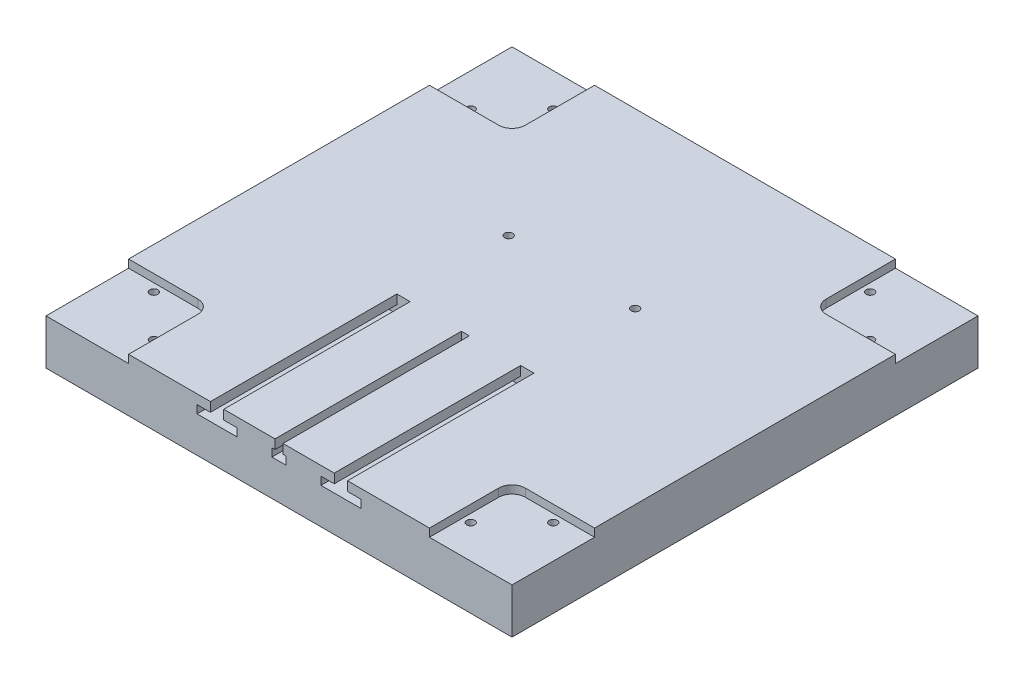
SolidWorks part; units mm, degrees
ref_plane "Front Plane" through (0, 0, 0) normal (0, 0, 1) x (1, 0, 0)
ref_plane "Top Plane" through (0, 0, 0) normal (0, 1, 0) x (1, 0, 0)
ref_plane "Right Plane" through (0, 0, 0) normal (1, 0, 0) x (0, 0, -1)
sketch "Sketch1" plane through (0, 0, 0) normal (0, 1, 0) x (1, 0, 0)
  line L0 (0, 87.5) -> (0, -87.5) construction
  line L1 (-87.5, 87.5) -> (87.5, 87.5)
  line L2 (-87.5, 87.5) -> (-87.5, -87.5)
  line L3 (-87.5, -87.5) -> (87.5, -87.5)
  line L4 (87.5, 87.5) -> (87.5, -87.5)
  line L5 (-87.5, 87.5) -> (87.5, -87.5) construction
  line L6 (-87.5, -87.5) -> (87.5, 87.5) construction
  line L15 (-87.5, 0) -> (87.5, 0) construction
  point P0 (0, 0)
  dimension "D1" = 175
  dimension "D2" = 175
extrude "Boss-Extrude2" add sketch "Sketch1" along normal blind 20
sketch "Sketch7" plane through (0, 20, 0) normal (0, 1, 0) x (1, 0, 0)
  line L0 (0, 87.5) -> (0, -87.5) construction
  line L1 (-87.5, 87.5) -> (-56.5, 87.5)
  line L2 (-87.5, 87.5) -> (-87.5, 56.5)
  line L3 (-87.5, 56.5) -> (-61.5, 56.5)
  line L4 (-56.5, 87.5) -> (-56.5, 61.5)
  line L5 (87.5, 87.5) -> (-87.5, 87.5) construction
  line L6 (-87.5, -87.5) -> (87.5, -87.5) construction
  line L7 (-87.5, 0) -> (87.5, 0) construction
  line L8 (-87.5, 87.5) -> (-87.5, -87.5) construction
  line L9 (87.5, -87.5) -> (87.5, 87.5) construction
  line L10 (87.5, 56.5) -> (61.5, 56.5)
  line L11 (56.5, 87.5) -> (56.5, 61.5)
  line L12 (87.5, 87.5) -> (56.5, 87.5)
  line L13 (87.5, 87.5) -> (87.5, 56.5)
  line L14 (87.5, -87.5) -> (87.5, -56.5)
  line L15 (87.5, -87.5) -> (56.5, -87.5)
  line L16 (56.5, -87.5) -> (56.5, -61.5)
  line L17 (87.5, -56.5) -> (61.5, -56.5)
  line L18 (-56.5, -87.5) -> (-56.5, -61.5)
  line L19 (-87.5, -56.5) -> (-61.5, -56.5)
  line L20 (-87.5, -87.5) -> (-87.5, -56.5)
  line L21 (-87.5, -87.5) -> (-56.5, -87.5)
  arc A0 (-61.5, 56.5) -> (-56.5, 61.5) centre (-61.5, 61.5) ccw
  arc A1 (61.5, 56.5) -> (56.5, 61.5) centre (61.5, 61.5) cw
  arc A2 (61.5, -56.5) -> (56.5, -61.5) centre (61.5, -61.5) ccw
  arc A3 (-61.5, -56.5) -> (-56.5, -61.5) centre (-61.5, -61.5) cw
  point P7 (-56.5, 56.5)
  point P38 (-56.5, -56.5)
  dimension "D3" = 5
  dimension "D1" = 31
  dimension "D2" = 31
extrude "Cut-Extrude6" cut sketch "Sketch7" against normal blind 3
sketch "Sketch8" plane through (0, 17, 0) normal (0, 1, 0) x (1, 0, 0)
  line L0 (-75, -62.5) -> (-75, -56.5) construction
  line L5 (-61.5, -56.5) -> (-87.5, -56.5) construction
  line L6 (-62.5, -75) -> (-56.5, -75) construction
  line L7 (-56.5, -87.5) -> (-56.5, -61.5) construction
  line L8 (-87.5, -87.5) -> (-56.5, -87.5) construction
  line L9 (-87.5, -56.5) -> (-87.5, -87.5) construction
  line L10 (0, 87.5) -> (0, -87.5) construction
  line L11 (56.5, 87.5) -> (-56.5, 87.5) construction
  line L12 (-56.5, -87.5) -> (56.5, -87.5) construction
  line L13 (62.5, -75) -> (56.5, -75) construction
  line L14 (75, -62.5) -> (75, -56.5) construction
  line L15 (-87.5, 0) -> (87.5, 0) construction
  line L16 (-87.5, 56.5) -> (-87.5, -56.5) construction
  line L17 (87.5, -56.5) -> (87.5, 56.5) construction
  circle A0 centre (-75, -59.5) radius 1.5
  circle A1 centre (-59.5, -75) radius 1.5
  circle A2 centre (59.5, -75) radius 1.5
  circle A3 centre (75, -59.5) radius 1.5
  circle A4 centre (59.5, 75) radius 1.5
  circle A5 centre (75, 59.5) radius 1.5
  circle A6 centre (-59.5, 75) radius 1.5
  circle A7 centre (-75, 59.5) radius 1.5
  dimension "D3" = 3
  dimension "D4" = 3
  dimension "D1" = 28
  dimension "D2" = 28
  dimension "D5" = 12.5
  dimension "D6" = 12.5
extrude "Cut-Extrude7" cut sketch "Sketch8" against normal up to next
sketch "Sketch9" plane through (0, 0, 87.5) normal (0, 0, 1) x (1, 0, 0)
  line L0 (0, 20) -> (0, 0) construction
  line L1 (-56.5, 20) -> (56.5, 20) construction
  line L2 (0, 10) -> (-46.5, 10) construction
  line L3 (-46.5, 20) -> (46.5, 20)
  line L4 (-46.5, 20) -> (-46.5, 0)
  line L5 (-46.5, 0) -> (46.5, 0)
  line L6 (46.5, 20) -> (46.5, 0)
  line L7 (-46.5, 20) -> (46.5, 0) construction
  line L8 (-46.5, 0) -> (46.5, 20) construction
  line L9 (-46.5, 10) -> (0, 10) construction
  line L10 (-20.75, 16.5) -> (-15.75, 16.5)
  line L11 (-23.25, 10) -> (-23.25, 20) construction
  line L12 (-30.75, 16.5) -> (-25.75, 16.5)
  line L13 (-30.75, 16.5) -> (-30.75, 13.5)
  line L14 (-30.75, 13.5) -> (-15.75, 13.5)
  line L15 (-15.75, 16.5) -> (-15.75, 13.5)
  line L16 (-30.75, 16.5) -> (-15.75, 13.5) construction
  line L17 (-30.75, 13.5) -> (-15.75, 16.5) construction
  line L18 (-25.75, 20) -> (-20.75, 20)
  line L19 (-25.75, 20) -> (-25.75, 16.5)
  line L21 (-20.75, 20) -> (-20.75, 16.5)
  line L22 (-25.75, 20) -> (-20.75, 16.5) construction
  line L23 (-25.75, 16.5) -> (-20.75, 20) construction
  line L24 (25.75, 16.5) -> (20.75, 20) construction
  line L25 (25.75, 20) -> (20.75, 16.5) construction
  line L26 (30.75, 13.5) -> (15.75, 16.5) construction
  line L27 (30.75, 16.5) -> (15.75, 13.5) construction
  line L28 (20.75, 20) -> (20.75, 16.5)
  line L29 (25.75, 20) -> (25.75, 16.5)
  line L30 (25.75, 20) -> (20.75, 20)
  line L31 (15.75, 16.5) -> (15.75, 13.5)
  line L32 (30.75, 13.5) -> (15.75, 13.5)
  line L33 (30.75, 16.5) -> (30.75, 13.5)
  line L34 (30.75, 16.5) -> (25.75, 16.5)
  line L35 (20.75, 16.5) -> (15.75, 16.5)
  line L36 (-15.75, 15) -> (15.75, 15) construction
  line L37 (1.5, 16.5) -> (2.65, 16.5)
  line L38 (-2.65, 16.5) -> (-1.5, 16.5)
  line L39 (-2.65, 16.5) -> (-2.65, 13.5)
  line L40 (-2.65, 13.5) -> (2.65, 13.5)
  line L41 (2.65, 16.5) -> (2.65, 13.5)
  line L42 (-2.65, 16.5) -> (2.65, 13.5) construction
  line L43 (-2.65, 13.5) -> (2.65, 16.5) construction
  line L44 (-1.5, 20) -> (1.5, 20)
  line L45 (-1.5, 20) -> (-1.5, 16.5)
  line L47 (1.5, 20) -> (1.5, 16.5)
  line L48 (-1.5, 20) -> (1.5, 16.5) construction
  line L49 (-1.5, 16.5) -> (1.5, 20) construction
  point P5 (0, 10)
  point P13 (-23.25, 15)
  point P19 (-23.25, 18.25)
  point P32 (23.25, 18.25)
  point P33 (23.25, 15)
  point P36 (0, 15)
  point P41 (0, 18.25)
  dimension "D1" = 93
  dimension "D2" = 20
  dimension "D3" = 3
  dimension "D4" = 15
  dimension "D5" = 3.5
  dimension "D6" = 5
  dimension "D7" = 5.3
  dimension "D8" = 3
  dimension "D9" = 3.5
  dimension "D10" = 3
  dimension "D11" = 46.5
extrude "Cut-Extrude8" cut sketch "Sketch9" against normal blind 70 contours L21 L3 L19 L12 L13 L14 L15 L10 | L28 L35 L31 L32 L33 L34 L29 L3 | L38 L45 L44 L47 L37 L41 L40 L39 region at (-23.25, 15.91, 87.5) region at (23.25, 15.91, 87.5)
sketch "Sketch10" plane through (0, 20, 0) normal (0, 1, 0) x (1, 0, 0)
  line L0 (56.5, 87.5) -> (-56.5, 87.5) construction
  line L1 (-23.75, 22.5) -> (23.75, 22.5) construction
  line L3 (87.5, -56.5) -> (87.5, 56.5) construction
  circle A0 centre (-23.75, 22.5) radius 1.5
  circle A1 centre (23.75, 22.5) radius 1.5
  point P2 (0, 87.5)
  point P3 (0, 22.5)
  point P7 (0, 32.5)
  dimension "D1" = 3
  dimension "D2" = 3
  dimension "D3" = 47.5
  dimension "D4" = 55
  dimension "D5" = 87.5
extrude "Cut-Extrude9" cut sketch "Sketch10" against normal up to next
